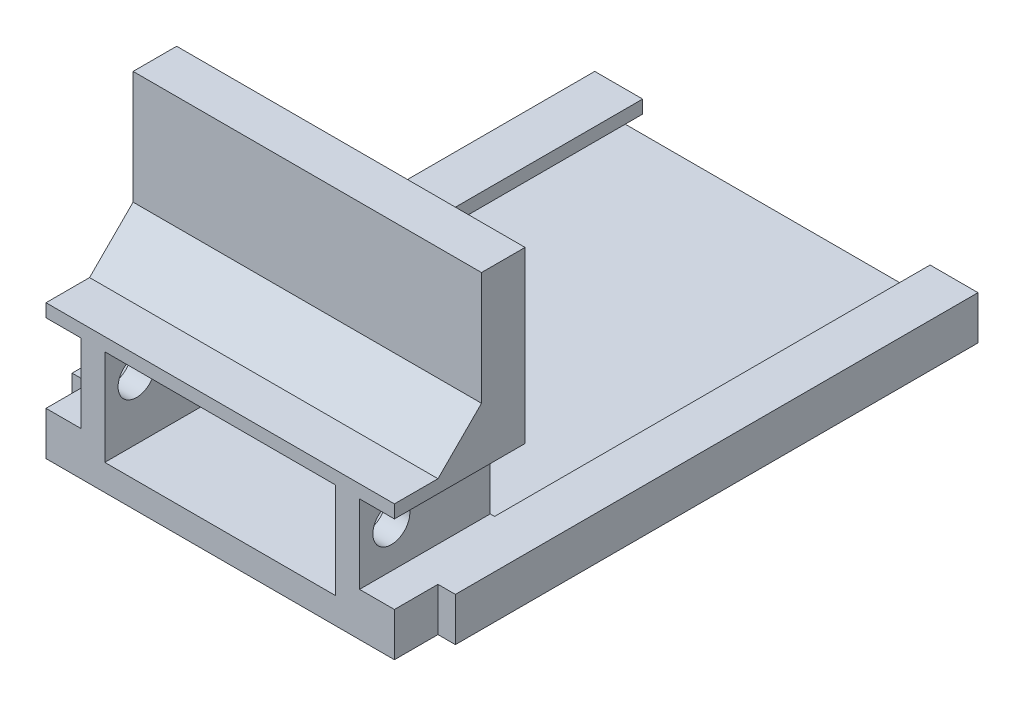
SolidWorks part; units mm, degrees
ref_plane "Front Plane" through (0, 0, 0) normal (0, 0, 1) x (1, 0, 0)
ref_plane "Top Plane" through (0, 0, 0) normal (0, 1, 0) x (1, 0, 0)
ref_plane "Right Plane" through (0, 0, 0) normal (1, 0, 0) x (0, 0, -1)
sketch "Sketch1" plane through (0, 0, 0) normal (0, 0, 1) x (1, 0, 0)
  line L1 (0, 0) -> (88, 0)
  line L2 (0, 0) -> (0, -10)
  line L3 (0, -10) -> (88, -10)
  line L4 (88, 0) -> (88, -10)
  line L5 (11, 0) -> (77, 0)
  line L6 (11, 0) -> (11, -3)
  line L7 (11, -3) -> (77, -3)
  line L8 (77, 0) -> (77, -3)
  line L9 (3, -3) -> (85, -3)
  line L10 (3, -3) -> (3, -7)
  line L11 (3, -7) -> (85, -7)
  line L12 (85, -3) -> (85, -7)
  point P12 (0, 0)
  point P14 (0, 0)
  point P15 (4.3368, -5.5)
  point P16 (6.3235, -3.7543)
  dimension "D1" = 88
  dimension "D2" = 10
  dimension "D3" = 3
  dimension "D4" = 4
  dimension "D5" = 82
  dimension "D6" = 3
  dimension "D7" = 66
  dimension "D8" = 11
extrude "Boss-Extrude1" add sketch "Sketch1" along normal blind 100 contours L9 L12 L11 L10 L6 L1 L2 L3 L4 L8 region at (5.5, -0.8857, 0)
sketch "Sketch2" plane through (0, 0, 100) normal (0, 0, 1) x (1, 0, 0)
  line L0 (44, 57) -> (44, 0) construction
  line L1 (0, -10) -> (88, -10)
  line L2 (0, -10) -> (0, 0)
  line L3 (0, 0) -> (88, 0)
  line L4 (88, -10) -> (88, 0)
  line L5 (4, 0) -> (84, 0)
  line L6 (4, 0) -> (4, 57)
  line L7 (4, 57) -> (84, 57)
  line L8 (84, 0) -> (84, 57)
  line L9 (44, 0) -> (44, -10) construction
  line M11 (77, -3) -> (85, -3)
  line M12 (85, -3) -> (85, -7)
  line M13 (85, -7) -> (3, -7)
  line M14 (3, -7) -> (3, -3)
  line M15 (3, -3) -> (11, -3)
  line M16 (11, -3) -> (11, 0)
  line M17 (11, 0) -> (0, 0)
  line M18 (0, 0) -> (0, -10)
  line M19 (0, -10) -> (88, -10)
  line M20 (88, -10) -> (88, 0)
  line M21 (88, 0) -> (77, 0)
  line M22 (77, 0) -> (77, -3)
  dimension "D1" = 67
  dimension "D2" = 80
extrude "Boss-Extrude2" add sketch "Sketch2" along normal blind 20 contours L3 M16 M15 M14 M13 M12 M11 M22 | L3 L8 L7 L6 M17 | L3 M22 M11 M12 M13 M14 M15 M16 M17 M18 M19 M20 M21 region at (0.8857, -5, 100) region at (44, 28.5, 100) region at (44, -3.6825, 100)
sketch "Sketch4" plane through (0, 0, 120) normal (0, 0, 1) x (1, 0, 0)
  line L0 (4, 0) -> (4, 57) construction
  line L1 (4, -10) -> (84, -10)
  line L2 (4, -10) -> (4, 21)
  line L3 (4, 21) -> (84, 21)
  line L4 (84, -10) -> (84, 21)
  line L6 (84, 0) -> (84, 57) construction
  dimension "D1" = 31
extrude "Boss-Extrude3" add sketch "Sketch4" along normal blind 10
extrude "Boss-Extrude4" add sketch "Sketch4<2>" against normal up to surface (20 mm away) up to face at (44, 7.3333, 100)
sketch "Sketch4<2>" plane through (0, 0, 120) normal (0, 0, 1) x (1, 0, 0) same geometry as "Sketch4"
sketch "Sketch5" plane through (0, 0, 130) normal (0, 0, 1) x (1, 0, 0)
  line L0 (44, 21) -> (44, -10) construction
  line L1 (17.5, 18) -> (70.5, 18)
  line L2 (17.5, 18) -> (17.5, -4)
  line L3 (17.5, -4) -> (70.5, -4)
  line L4 (70.5, 18) -> (70.5, -4)
  line L5 (84, 21) -> (4, 21) construction
  line L6 (4, -10) -> (84, -10) construction
  line L7 (44, 18) -> (44, -4) construction
  line L8 (4, 21) -> (4, -10) construction
  line L9 (4, 18) -> (12, 18)
  line L10 (4, 18) -> (4, 0)
  line L11 (4, 0) -> (12, 0)
  line L12 (12, 18) -> (12, 0)
  line L13 (84, -10) -> (84, 21) construction
  line L14 (84, 18) -> (76, 18)
  line L15 (84, 18) -> (84, 0)
  line L16 (84, 0) -> (76, 0)
  line L17 (76, 18) -> (76, 0)
  dimension "D1" = 6
  dimension "D2" = 22
  dimension "D3" = 53
  dimension "D4" = 18
  dimension "D5" = 18
  dimension "D6" = 5.5
  dimension "D7" = 5.5
extrude "Cut-Extrude1" cut sketch "Sketch5" against normal up to surface (30 mm away) up to face at (44, 7.3333, 100)
sketch "Sketch6" plane through (4, 0, 0) normal (-1, 0, 0) x (0, 0, 1)
  line L0 (120, 57) -> (100, 57) construction
  line L1 (110, 57) -> (120, 57)
  line L2 (110, 57) -> (110, 21)
  line L3 (110, 21) -> (120, 21)
  line L4 (120, 57) -> (120, 21)
extrude "Cut-Extrude2" cut sketch "Sketch6" against normal up to surface (80 mm away) up to face at (84, 32, 116.6667)
sketch "Sketch7" plane through (76, 0, 0) normal (1, 0, 0) x (0, 0, -1)
  line L0 (-100, 9.5) -> (-122.7, 9.5)
  line L1 (-100, 0) -> (-100, 18) construction
  line L2 (-100, 0) -> (-130, 0) construction
  circle A0 centre (-122.7, 9.5) radius 4.25
  point P5 (0, 0)
  point P6 (0, 0)
  dimension "D3" = 8.5
  dimension "D1" = 22.7
  dimension "D2" = 9.5
extrude "Cut-Extrude3" cut sketch "Sketch7" against normal through all contours A0
chamfer "Chamfer1" distance 10 angle 45 1 edges at (44, 21, 110)
